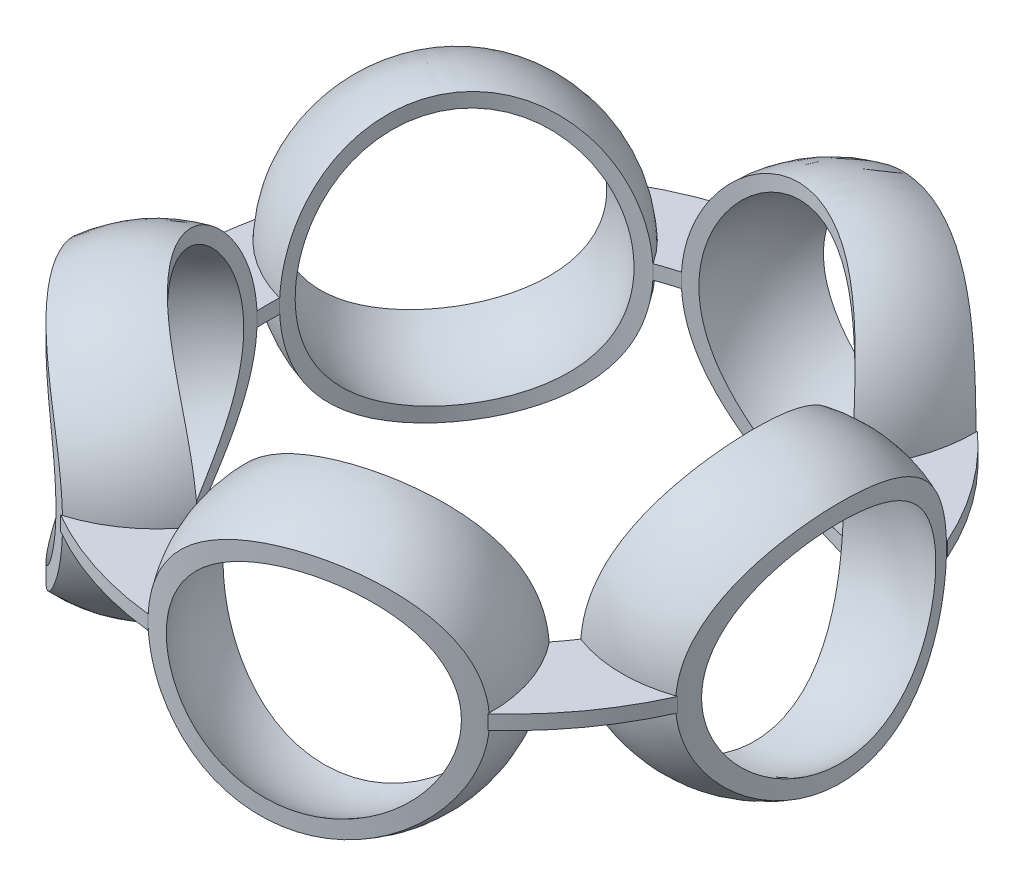
SolidWorks part; units mm, degrees
ref_plane "Front" through (0, 0, 0) normal (0, 0, 1) x (1, 0, 0)
ref_plane "Top" through (0, 0, 0) normal (0, 1, 0) x (1, 0, 0)
ref_plane "Right" through (0, 0, 0) normal (1, 0, 0) x (0, 0, -1)
sketch "Sketch1" plane through (0, 0, 0) normal (0, 1, 0) x (1, 0, 0)
  line L0 (3.55, 2) -> (3.55, 1.8)
  line L1 (3.55, -1.8) -> (3.55, -2)
  arc A0 (3.55, -2) -> (3.55, 2) centre (3.55, 0) ccw
  arc A1 (3.55, -1.8) -> (3.55, 1.8) centre (3.55, 0) ccw
  dimension "D1" = 3.55
revolve "Revolve1" add sketch "Sketch1" angle 360 about L0
ref_axis "Axis1" through (0, 50, 0) along (0, -1, 0)
pattern_circular "CirPattern2" count 5 over 360 about axis through (0, 50, 0) along (0, -1, 0) of bodies 103
sketch "Sketch2" plane through (0, 0, 0) normal (0, 1, 0) x (1, 0, 0)
  circle A0 centre (0, 0) radius 4.6
  circle A1 centre (0, 0) radius 6
extrude "Cut-Extrude1" cut sketch "Sketch2" against normal blind 5 and the other way blind 10
sketch "Sketch3" plane through (0, 0, 0) normal (0, 1, 0) x (1, 0, 0)
  circle A0 centre (0, 0) radius 3.4
extrude "Cut-Extrude2" cut sketch "Sketch3" against normal blind 5 and the other way blind 5
sketch "Sketch4" plane through (0, 0, 0) normal (0, 1, 0) x (1, 0, 0)
  arc A0 (-0.4931, 4.5893) -> (-2.2986, 4.0027) centre (0, 0) ccw
  arc A1 (-0.9006, 3.2786) -> (-1.1985, 3.1818) centre (0, 0) ccw
  arc A2 (-0.5061, 4.5721) -> (-0.9006, 3.2786) centre (1.097, 3.3763) ccw construction
  arc A3 (-1.1985, 3.1818) -> (-2.2779, 3.9964) centre (-2.872, 2.0866) ccw construction
  arc A4 (-4.5047, 0.9315) -> (-3.3964, 0.1566) centre (-2.872, 2.0866) ccw construction
  arc A5 (-3.3964, -0.1566) -> (-4.5047, -0.9315) centre (-2.872, -2.0866) ccw construction
  arc A6 (-2.2779, -3.9964) -> (-1.1985, -3.1818) centre (-2.872, -2.0866) ccw construction
  arc A7 (-0.9006, -3.2786) -> (-0.5061, -4.5721) centre (1.097, -3.3763) ccw construction
  arc A8 (3.0969, -3.4014) -> (2.6557, -2.123) centre (1.097, -3.3763) ccw construction
  arc A9 (2.8398, -1.8697) -> (4.1919, -1.8942) centre (3.55, 0) ccw construction
  arc A10 (4.1919, 1.8942) -> (2.8398, 1.8697) centre (3.55, 0) ccw construction
  arc A11 (2.6557, 2.123) -> (3.0969, 3.4014) centre (1.097, 3.3763) ccw construction
  arc A12 (-0.4931, 4.5893) -> (-0.9006, 3.2786) centre (1.097, 3.3763) ccw
  arc A13 (-1.1985, 3.1818) -> (-2.2986, 4.0027) centre (-2.872, 2.0866) ccw
  arc A14 (-4.5171, 0.9492) -> (-3.3964, 0.1566) centre (-2.872, 2.0866) ccw
  arc A15 (-3.3964, -0.1566) -> (-4.5171, -0.9492) centre (-2.872, -2.0866) ccw
  arc A16 (-2.2986, -4.0027) -> (-1.1985, -3.1818) centre (-2.872, -2.0866) ccw
  arc A17 (-0.9006, -3.2786) -> (-0.4931, -4.5893) centre (1.097, -3.3763) ccw
  arc A18 (3.0965, -3.423) -> (2.6557, -2.123) centre (1.097, -3.3763) ccw
  arc A19 (2.8398, -1.8697) -> (4.2124, -1.8871) centre (3.55, 0) ccw
  arc A20 (4.2124, 1.8871) -> (2.8398, 1.8697) centre (3.55, 0) ccw
  arc A21 (2.6557, 2.123) -> (3.0965, 3.423) centre (1.097, 3.3763) ccw
  arc A22 (-3.3964, 0.1566) -> (-3.3964, -0.1566) centre (0, 0) ccw
  arc A23 (-4.5171, 0.9492) -> (-4.5171, -0.9492) centre (0, 0) ccw
  arc A24 (-1.1985, -3.1818) -> (-0.9006, -3.2786) centre (0, 0) ccw
  arc A25 (-2.2986, -4.0027) -> (-0.4931, -4.5893) centre (0, 0) ccw
  arc A26 (2.6557, -2.123) -> (2.8398, -1.8697) centre (0, 0) ccw
  arc A27 (3.0965, -3.423) -> (4.2124, -1.8871) centre (0, 0) ccw
  arc A28 (2.8398, 1.8697) -> (2.6557, 2.123) centre (0, 0) ccw
  arc A29 (4.2124, 1.8871) -> (3.0965, 3.423) centre (0, 0) ccw
extrude "Boss-Extrude1" add sketch "Sketch4" along normal mid plane 0.2 separate body
